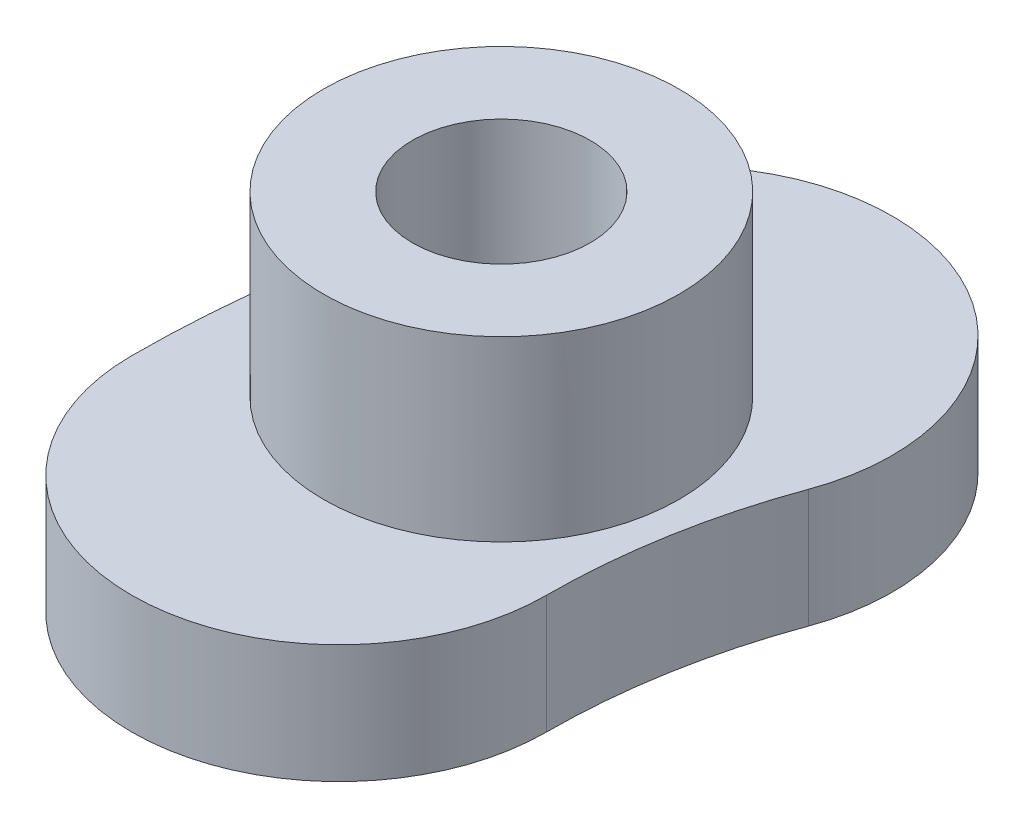
SolidWorks part; units mm, degrees
note: The reader was unsure of these and kept them because the rebuilt part matched: shared geometry of "草图2<3>".
ref_plane "前视基准面" through (0, 0, 0) normal (0, 0, 1) x (1, 0, 0)
ref_plane "上视基准面" through (0, 0, 0) normal (0, 1, 0) x (1, 0, 0)
ref_plane "右视基准面" through (0, 0, 0) normal (1, 0, 0) x (0, 0, -1)
sketch "草图2" plane through (0, 0, 0) normal (0, 1, 0) x (1, 0, 0)
  line L0 (-14.5, 0) -> (0, 0) construction
  line L1 (0, 0) -> (-13.6255, 4.9593) construction
  arc A0 (-14.5, 0) -> (-13.6255, 4.9593) centre (0, 0) cw construction
  arc A1 (-16.9145, 6.1564) -> (-18, 0) centre (0, 0) ccw
  arc A2 (-10.3366, 3.7622) -> (-11, 0) centre (0, 0) ccw
  arc A3 (-10.3366, 3.7622) -> (-16.9145, 6.1564) centre (-13.6255, 4.9593) ccw
  arc A4 (-18, 0) -> (-11, 0) centre (-14.5, 0) ccw
  circle A5 centre (-14.2797, 2.5179) radius 1.5
  point P3 (-14.2797, 2.5179)
  dimension "D1" = 14.5
  dimension "D3" = 11
  dimension "D4" = 3
  dimension "D2" = 20
extrude "凸台-拉伸1" add sketch "草图2" along normal blind 2 contours A1 A4 A2 A3 A5
extrude "拉伸-薄壁1" add sketch "草图2<3>" along normal blind 5 thin contours A5
sketch "草图2<3>" plane through (0, 0, 0) normal (0, 1, 0) x (1, 0, 0) same geometry as "草图2"
equation "\"D3@草图2\"=\"D1@草图2\"-3.5"
